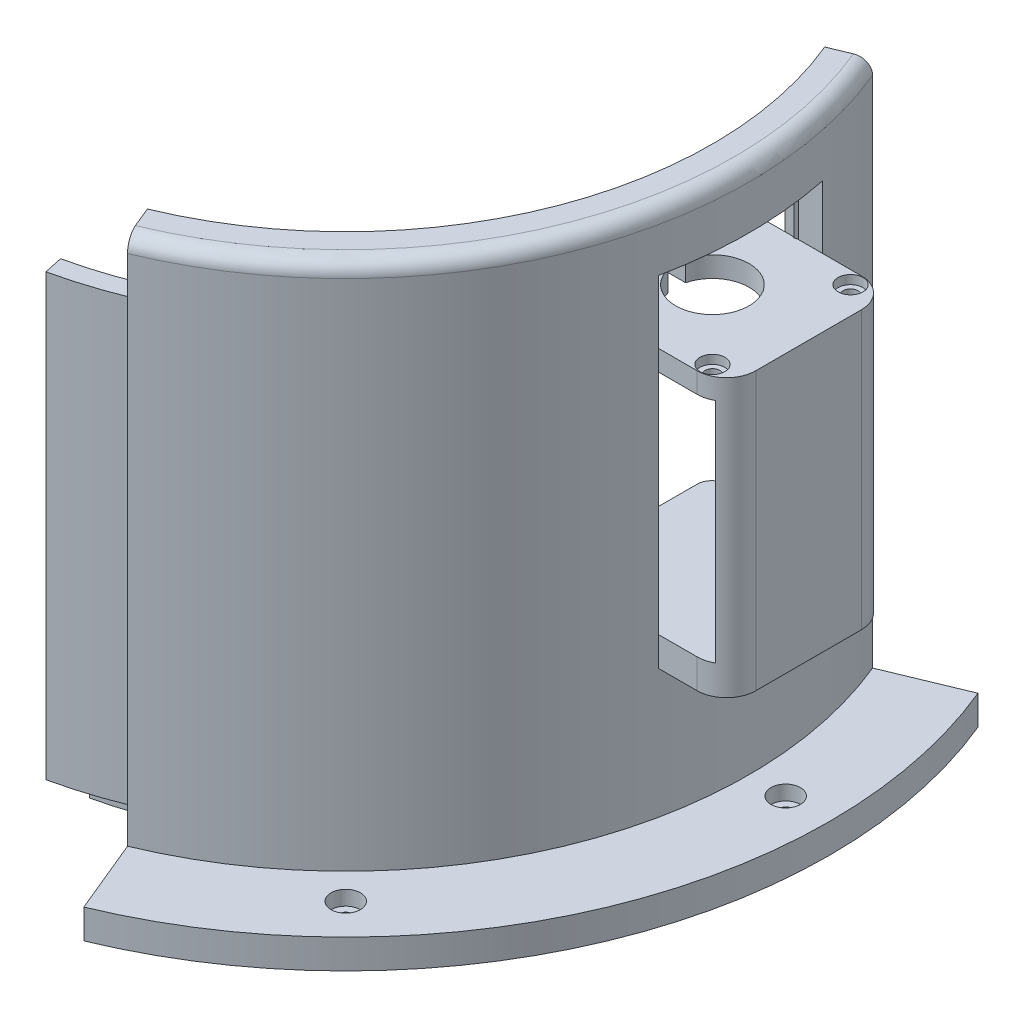
SolidWorks part; units mm, degrees
ref_plane "Front Plane" through (0, 0, 0) normal (0, 0, 1) x (1, 0, 0)
ref_plane "Top Plane" through (0, 0, 0) normal (0, 1, 0) x (1, 0, 0)
ref_plane "Right Plane" through (0, 0, 0) normal (1, 0, 0) x (0, 0, -1)
sketch "Sketch1" plane through (0, 0, 0) normal (0, 1, 0) x (1, 0, 0)
  circle A6 centre (0, 0) radius 125
  circle A7 centre (0, 0) radius 137.5
  dimension "D1" = 250
  dimension "D2" = 275
extrude "Boss-Extrude1" add sketch "Sketch1" along normal blind 180
sketch "Sketch2" plane through (0, 0, 0) normal (0, -1, 0) x (1, 0, 0)
  circle A0 centre (0, 0) radius 165
  circle A1 centre (0, 150) radius 2.5
  circle A2 centre (0, 30) radius 2.5
  circle A3 centre (106.066, 106.066) radius 2.5
  circle A4 centre (150, 0) radius 2.5
  circle A5 centre (106.066, -106.066) radius 2.5
  circle A6 centre (0, -150) radius 2.5
  circle A7 centre (-106.066, -106.066) radius 2.5
  circle A8 centre (-150, 0) radius 2.5
  circle A9 centre (-106.066, 106.066) radius 2.5
  circle A10 centre (21.2132, 21.2132) radius 2.5
  circle A11 centre (30, 0) radius 2.5
  circle A12 centre (21.2132, -21.2132) radius 2.5
  circle A13 centre (0, -30) radius 2.5
  circle A14 centre (-21.2132, -21.2132) radius 2.5
  circle A15 centre (-30, 0) radius 2.5
  circle A16 centre (-21.2132, 21.2132) radius 2.5
  point P24 (0, 0)
  point P39 (0, 0)
  dimension "D1" = 330
  dimension "D3" = 5
  dimension "D4" = 8
  dimension "D5" = 5
  dimension "D2" = 150
  dimension "D6" = 30
  dimension "D7" = 8
extrude "Boss-Extrude2" add sketch "Sketch2" along normal blind 10
sketch "Sketch3" plane through (0, 0, 0) normal (0, 1, 0) x (1, 0, 0)
  circle A0 centre (0, 0) radius 47.5
  circle A1 centre (0, 0) radius 52.5
  dimension "D1" = 95
  dimension "D2" = 105
extrude "Boss-Extrude3" add sketch "Sketch3" along normal blind 20
sketch "Sketch4" plane through (0, 0, 0) normal (1, 0, 0) x (0, 0, -1)
  line L0 (137.5, 180) -> (-137.5, 180) construction
  line L1 (-28, 160) -> (28, 160)
  line L2 (-28, 160) -> (-28, 54)
  line L3 (-28, 54) -> (28, 54)
  line L4 (28, 160) -> (28, 54)
  line L5 (-28, 160) -> (28, 54) construction
  line L6 (-28, 54) -> (28, 160) construction
  point P0 (0, 107)
  dimension "D1" = 56
  dimension "D2" = 106
  dimension "D3" = 20
extrude "Cut-Extrude4" cut sketch "Sketch4" along normal blind 150
sketch "Sketch5" plane through (0, 0, 28) normal (0, 0, -1) x (-1, 0, 0)
  line L0 (-121.8236, 160) -> (-121.8236, 54) construction
  line L1 (-152.8236, 138.5) -> (-96.8236, 138.5)
  line L2 (-152.8236, 138.5) -> (-152.8236, 131.5)
  line L3 (-152.8236, 131.5) -> (-96.8236, 131.5)
  line L4 (-96.8236, 138.5) -> (-96.8236, 131.5)
  line L5 (-152.8236, 138.5) -> (-96.8236, 131.5) construction
  line L6 (-152.8236, 131.5) -> (-96.8236, 138.5) construction
  line L7 (-137.5, 160) -> (-134.6189, 160) construction
  point P0 (-124.8236, 135)
  dimension "D1" = 7
  dimension "D2" = 25
  dimension "D3" = 56
  dimension "D4" = 3
extrude "Boss-Extrude4" add sketch "Sketch5" along normal up to surface (56 mm away) up to face at (128.2213, 107, -28)
sketch "Sketch6" plane through (0, 54, 0) normal (0, 1, 0) x (1, 0, 0)
  line L1 (96.8236, 28) -> (152.8236, 28)
  line L2 (96.8236, 28) -> (96.8236, -28)
  line L3 (96.8236, -28) -> (152.8236, -28)
  line L4 (152.8236, 28) -> (152.8236, -28)
extrude "Boss-Extrude5" add sketch "Sketch6" against normal blind 10
sketch "Sketch7" plane through (0, 138.5, 0) normal (0, 1, 0) x (1, 0, 0)
  line L0 (96.8236, 28) -> (96.8236, -28) construction
  line L1 (101.4736, 23.55) -> (148.5736, 23.55) construction
  line L2 (101.4736, 23.55) -> (101.4736, -23.55) construction
  line L3 (101.4736, -23.55) -> (148.5736, -23.55) construction
  line L4 (148.5736, 23.55) -> (148.5736, -23.55) construction
  line L5 (101.4736, 23.55) -> (148.5736, -23.55) construction
  line L6 (101.4736, -23.55) -> (148.5736, 23.55) construction
  circle A0 centre (101.4736, 23.55) radius 2.5
  circle A1 centre (148.5736, 23.55) radius 2.5
  circle A2 centre (101.4736, -23.55) radius 2.5
  circle A3 centre (148.5736, -23.55) radius 2.5
  circle A4 centre (125.0236, 0) radius 12.5
  dimension "D3" = 25
  dimension "D4" = 5
  dimension "D1" = 47.1
  dimension "D2" = 47.1
  dimension "D5" = 28.2
extrude "Cut-Extrude5" cut sketch "Sketch7" against normal blind 10
sketch "Sketch8" plane through (152.8236, 0, 0) normal (1, 0, 0) x (0, 0, -1)
  line L1 (-28, 138.5) -> (28, 138.5)
  line L2 (-28, 138.5) -> (-28, 44)
  line L3 (-28, 44) -> (28, 44)
  line L4 (28, 138.5) -> (28, 44)
extrude "Boss-Extrude6" add sketch "Sketch8" along normal blind 5
fillet "Fillet1" radius 10 2 edges at (157.8236, 91.25, -28) (157.8236, 91.25, 28)
fillet "Fillet2" radius 5 4 edges at (96.8236, 49, -28) (96.8236, 49, 28) (96.8236, 135, 28) (96.8236, 135, -28)
sketch "Sketch9" plane through (0, 138.5, 0) normal (0, 1, 0) x (1, 0, 0)
  line L0 (96.8236, 23) -> (96.8236, -23) construction
  line L1 (80.7583, 3) -> (112.889, 3)
  line L2 (80.7583, 3) -> (80.7583, -3)
  line L3 (80.7583, -3) -> (112.889, -3)
  line L4 (112.889, 3) -> (112.889, -3)
  line L5 (80.7583, 3) -> (112.889, -3) construction
  line L6 (80.7583, -3) -> (112.889, 3) construction
  circle A0 centre (125.0236, 0) radius 12.5 construction
  point P0 (96.8236, 0)
  dimension "D1" = 6
extrude "Cut-Extrude6" cut sketch "Sketch9" against normal blind 10
fillet "Fillet3" radius 5 1 edges at (0, 180, 137.5)
sketch "Sketch10" plane through (0, 0, 0) normal (0, 1, 0) x (1, 0, 0)
  circle A0 centre (0, 0) radius 47.5
  dimension "D1" = 95
extrude "Cut-Extrude7" cut sketch "Sketch10" against normal blind 3
sketch "Sketch11" plane through (0, 0, 0) normal (0, 1, 0) x (1, 0, 0)
  circle A0 centre (0, 150) radius 5
  circle A1 centre (106.066, 106.066) radius 5
  circle A2 centre (150, 0) radius 5
  circle A3 centre (106.066, -106.066) radius 5
  circle A4 centre (0, -150) radius 5
  circle A5 centre (-106.066, -106.066) radius 5
  circle A6 centre (-150, 0) radius 5
  circle A7 centre (-106.066, 106.066) radius 5
  point P19 (0, 0)
  dimension "D1" = 10
  dimension "D2" = 8
extrude "Cut-Extrude8" cut sketch "Sketch11" against normal blind 5
sketch "Sketch13" plane through (0, 0, 0) normal (0, 0, 1) x (1, 0, 0)
  line L1 (-132, 176) -> (-118, 176)
  line L2 (-132, 176) -> (-132, 164)
  line L3 (-132, 164) -> (-118, 164)
  line L4 (-118, 176) -> (-118, 164)
  line L5 (-132, 176) -> (-118, 164) construction
  line L6 (-132, 164) -> (-118, 176) construction
  line L7 (0, 0) -> (0, 216.6626) construction
  line L8 (132.5, 180) -> (-132.5, 180) construction
  point P0 (-125, 170)
  dimension "D1" = 12
  dimension "D2" = 14
  dimension "D3" = 125
  dimension "D4" = 4
revolve "Cut-Revolve1" cut sketch "Sketch13" angle 360 about L7
sketch "Sketch14" plane through (0, 180, 0) normal (0, 1, 0) x (1, 0, 0)
  line L0 (0, 0) -> (152.4401, 63.1428)
  line L1 (0, 0) -> (-63.1428, 152.4401)
  line L2 (0, 0) -> (-152.4401, -63.1428)
  line L3 (0, 0) -> (63.1428, -152.4401)
  line L4 (0, 0) -> (165, 0) construction
  circle A0 centre (0, 0) radius 165 construction
  circle A1 centre (0, 0) radius 165
  circle M4 centre (0, 0) radius 132.5
  circle M5 centre (0, 0) radius 125
  dimension "D3" = 330
  dimension "D1" = 22.5
  dimension "D2" = 90
extrude "Cut-Extrude9" cut sketch "Sketch14" against normal through all contours L0 A1 L1 M4 | L1 L0 M5 M4 | L1 L0 M5 | L1 A1 L2 M4 | L2 L1 M5 M4 | L2 L1 M5 | L3 L2 M5 | L3 L2 M5 M4 | L2 A1 L3 M4 region at (28.7113, 180, -69.3153) region at (-69.3153, 180, -28.7113) region at (-28.7113, 180, 69.3153) region at (48.5729, 180, -117.2654) region at (-117.2654, 180, -48.5729) region at (-48.5729, 180, 117.2654) region at (51.4536, 180, -124.22) region at (-124.22, 180, -51.4536) region at (-51.4536, 180, 124.22)
sketch "Sketch15" plane through (0, 0, 0) normal (-0.9239, 0, 0.3827) x (0.3827, 0, 0.9239)
  line L0 (0, -10) -> (165, -10) construction
  line L1 (134.5, 160) -> (128, 160)
  line L2 (134.5, 160) -> (134.5, 10)
  line L3 (134.5, 10) -> (128, 10)
  line L4 (128, 160) -> (128, 10)
  line L5 (134.5, 160) -> (128, 10) construction
  line L6 (134.5, 10) -> (128, 160) construction
  line L7 (137.5, 0) -> (137.5, 175) construction
  line L8 (125, 0) -> (125, 164) construction
  line L10 (55, -7) -> (115, -7)
  line L11 (55, -7) -> (55, -3)
  line L12 (55, -3) -> (115, -3)
  line L13 (115, -7) -> (115, -3)
  line L14 (55, -7) -> (115, -3) construction
  line L15 (55, -3) -> (115, -7) construction
  line L16 (0, -10) -> (0, -3) construction
  line L17 (125, 0) -> (0, 0) construction
  line L18 (0, 0) -> (0, 180) construction
  point P0 (131.25, 85)
  point P11 (85, -5)
  point P18 (55, -5)
  dimension "D1" = 95
  dimension "D2" = 150
  dimension "D3" = 3
  dimension "D4" = 3
  dimension "D5" = 55
  dimension "D6" = 60
  dimension "D7" = 3
  dimension "D8" = 3
revolve "Revolve1" add sketch "Sketch15" angle 10 about L18 reverse direction yes
sketch "Sketch16" plane through (0, 0, 0) normal (-0.3827, 0, -0.9239) x (-0.9239, 0, 0.3827)
  line L0 (-125, 0) -> (-125, 164) construction
  line L1 (-134.5, 160) -> (-128, 160)
  line L2 (-134.5, 160) -> (-134.5, 10)
  line L3 (-134.5, 10) -> (-128, 10)
  line L4 (-128, 160) -> (-128, 10)
  line L5 (-134.5, 160) -> (-128, 10) construction
  line L6 (-134.5, 10) -> (-128, 160) construction
  line L7 (-115, -7) -> (-55, -7)
  line L8 (-115, -7) -> (-115, -3)
  line L9 (-115, -3) -> (-55, -3)
  line L10 (-55, -7) -> (-55, -3)
  line L11 (-115, -7) -> (-55, -3) construction
  line L12 (-115, -3) -> (-55, -7) construction
  line L13 (-137.5, 0) -> (-137.5, 175) construction
  line L14 (0, -10) -> (-165, -10) construction
  line L15 (-125, 0) -> (-52.5, 0) construction
  line L16 (0, 0) -> (0, 103.8679) construction
  line L17 (0, 0) -> (0, 164) construction
  point P0 (-131.25, 85)
  point P5 (-85, -5)
  dimension "D1" = 3
  dimension "D2" = 3
  dimension "D3" = 95
  dimension "D4" = 150
  dimension "D5" = 3
  dimension "D6" = 3
  dimension "D7" = 55
  dimension "D8" = 60
revolve "Cut-Revolve2" cut sketch "Sketch16" angle 10 about L16 reverse direction yes
sketch "Sketch17" plane through (0, -10, 0) normal (0, -1, 0) x (-1, 0, 0)
  circle A0 centre (0, 0) radius 40
  dimension "D1" = 80
extrude "Cut-Extrude10" cut sketch "Sketch17" against normal blind 3
sketch "Sketch18" plane through (0, 138.5, 0) normal (0, 1, 0) x (1, 0, 0)
  circle A0 centre (101.4736, 23.55) radius 4.25
  circle A1 centre (148.5736, 23.55) radius 4.25
  circle A2 centre (101.4736, -23.55) radius 4.25
  circle A3 centre (148.5736, -23.55) radius 4.25
  dimension "D1" = 8.5
extrude "Cut-Extrude12" cut sketch "Sketch18" against normal blind 3
